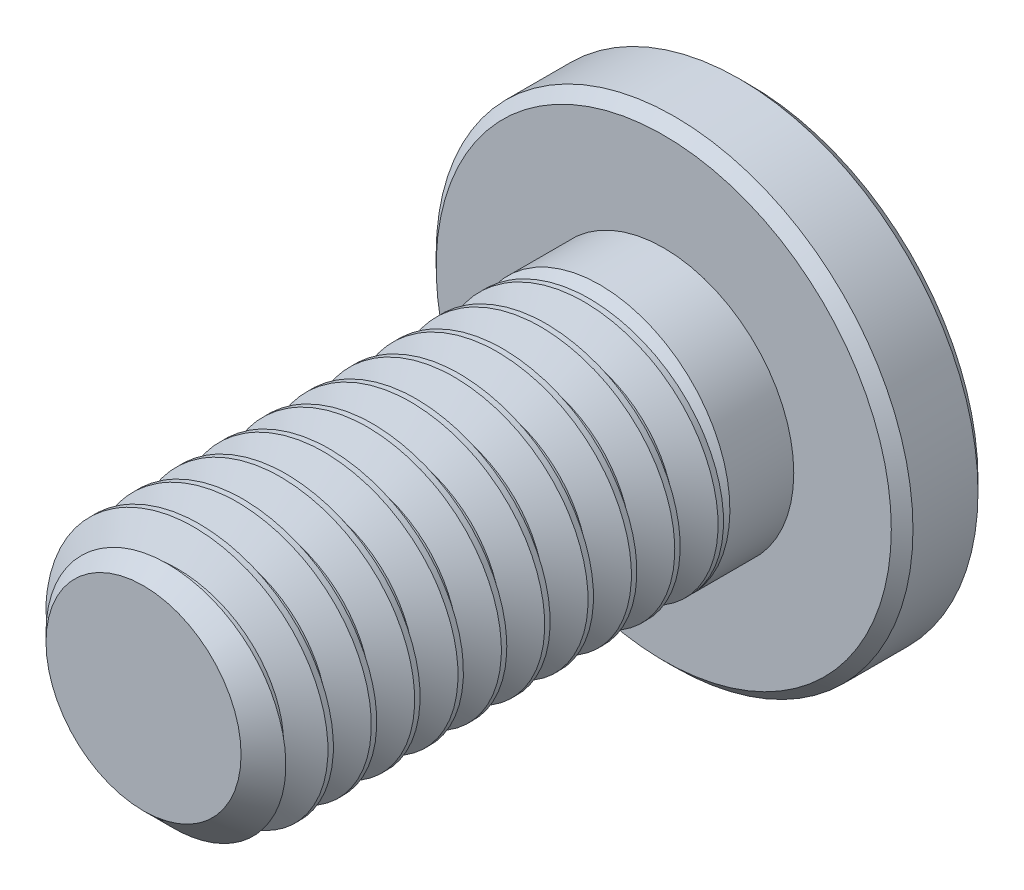
SolidWorks part; units mm, degrees
other "DetailItem1"
ref_plane "Front Plane" through (0, 0, 0) normal (0, 0, 1) x (1, 0, 0)
ref_plane "Top Plane" through (0, 0, 0) normal (0, 1, 0) x (1, 0, 0)
ref_plane "Right Plane" through (0, 0, 0) normal (1, 0, 0) x (0, 0, -1)
sketch "Sketch0" plane through (0, 0, 0) normal (1, 0, 0) x (0, 0, -1)
  line L0 (3.5, 0) -> (-3.5, 0) construction
  line L1 (3.5, 2.75) -> (3.5, -2.75) construction
  line L2 (3.5, 2.75) -> (2.5, 2.75) construction
  line L3 (-3.5, 0) -> (-3.5, 1.5) construction
  line L4 (-3.5, 1.5) -> (-3, 1.5) construction
  point P3 (3.5, 1)
  point P6 (3.5, 0)
  dimension "Head Diameter" = 5.5
  dimension "Drive Size" = 2
  dimension "Head Height" = 1
  dimension "Thread Pitch" = 0.5
  dimension "Thread Size" = 3
  dimension "Length" = 6
sketch "Sketch1" plane through (0, 0, 0) normal (0, 0, 1) x (1, 0, 0)
  circle A0 centre (0, 0) radius 1.5
extrude "Extrude1" add sketch "Sketch1" along normal up to vertex (3.5 mm away) from vertex up to point (0, 0, 3.5) starting at point (0, 2.75, -2.5)
sketch "Sketch6" plane through (0, 0, 0) normal (0, 0, 1) x (1, 0, 0)
  circle A0 centre (0, 0) radius 2.75
extrude "Extrude2" add sketch "Sketch6" along normal up to vertex (-2.5 mm away) from vertex up to point (0, 2.75, -2.5) starting at point (0, 2.75, -3.5)
sketch "Sketch7" plane through (0, 0, -3.5) normal (0, 0, 1) x (1, 0, 0)
  line L1 (0, 1.1547) -> (-1, 0.5774)
  line L2 (-1, 0.5774) -> (-1, -0.5774)
  line L3 (-1, -0.5774) -> (0, -1.1547)
  line L4 (0, -1.1547) -> (1, -0.5774)
  line L5 (1, -0.5774) -> (1, 0.5774)
  line L6 (1, 0.5774) -> (0, 1.1547)
  circle A0 centre (0, 0) radius 1 construction
extrude "Cut-Extrude1" cut sketch "Sketch7" along normal blind 0.75
sketch "Sketch8" plane through (0, 0, -3.5) normal (0, 0, 1) x (1, 0, 0)
  circle A0 centre (0, 0) radius 1.1547
extrude "Cut-Extrude2" cut sketch "Sketch8" along normal up to next (0.75 mm away) draft 45
chamfer "Chamfer1" distance 0.125 angle 45 2 edges at (2.75, 0, -2.5) (2.75, 0, -3.5)
chamfer "Chamfer2" distance 0.375 angle 45 1 edges at (1.5, 0, 3.5)
split "Split1" bodies to split 107 resulting bodies 110 111 split by face at (2.625, 0, -2.5)
sketch "Sketch2" plane through (0, 0, 3.5) normal (0, 0, -1) x (-1, 0, 0)
  circle A1 centre (0, 0) radius 1.5
curve "Helix/Spiral1" pitch 0.5 height 6.5 radius 1.5 centre (0, 0, 3.5) axis (0, 0, -1) start towards (0, 1, 0) parameters "pitch"=0.5
sketch "Sketch3" plane through (0, 0, 0) normal (1, 0, 0) x (0, 0, -1)
  line L0 (-3.9687, 1.5541) -> (-3.7187, 1.1211) construction
  line L1 (-3.7187, 1.1211) -> (-3.4687, 1.5541) construction
  line L2 (-3.4687, 1.5541) -> (-3.9687, 1.5541) construction
  line L3 (-3.9375, 1.5) -> (-3.5, 1.5) construction
  line L4 (-3.7187, 1.5541) -> (-3.7187, 1.5) construction
  line L5 (-3.7187, 1.5) -> (-3.7187, 1.1752) construction
  line L6 (-3.7187, 1.1752) -> (-3.7187, 1.1211) construction
  line L7 (-3.75, 1.1752) -> (-3.6875, 1.1752)
  line L8 (-3.9531, 1.5271) -> (-3.4844, 1.5271)
  line L9 (-3.6875, 1.1752) -> (-3.4844, 1.5271)
  line L10 (-3.75, 1.1752) -> (-3.9531, 1.5271)
  line L12 (-3.5, 0) -> (-3.5, 1.5) construction
  line L13 (-3.125, -1.5) -> (2.5, -1.5) construction
  point P14 (-3.7187, 1.5271)
  point P17 (-2.25, -1.5)
  dimension "D1" = 0.5
  dimension "D2" = 0.0625
  dimension "D3" = 1.25
sweep "Cut-Sweep1" cut profiles "Sketch3" path "Helix/Spiral1" align with end faces yes
sketch "Sketch9" plane through (0, 0, 0) normal (1, 0, 0) x (0, 0, -1)
  line L0 (2.5, 1.5) -> (1.7634, 1.5)
  line L1 (2.5, 2.625) -> (2.5, -2.625) construction
  line L2 (1.7634, 1.5) -> (1.3845, 1.1211)
  line L3 (1.3845, 1.1211) -> (1.3845, 0)
  line L4 (3.5, 0) -> (-3.5, 0) construction
  line L5 (1.3845, 0) -> (2.5, 0)
  line L6 (2.5, 0) -> (2.5, 1.5)
  dimension "D1" = 45
  dimension "Relief" = 0.7366
revolve "Revolve1" add sketch "Sketch9" angle 360 about L0
equation "\"D3@Helix/Spiral1\" = \"Length@Sketch0\" + \"Thread Pitch@Sketch0\""
equation "\"D1@Cut-Extrude1\"=\"Head Height@Sketch0\"*.75"
equation "\"D1@Chamfer1\" = \"Head Height@Sketch0\" * 0.125"
equation "\"pitch@Helix/Spiral1\" = \"Thread Pitch@Sketch0\""
equation "\"D2@Sketch3\"=\"D1@Sketch3\"/8"
equation "\"D1@Sketch3\" = \"Thread Pitch@Sketch0\""
equation "\"D3@Sketch3\" = \"Thread Pitch@Sketch0\" * 2.5"
equation "\"D1@Chamfer2\"=\"thread pitch@sketch0\"*0.75"
